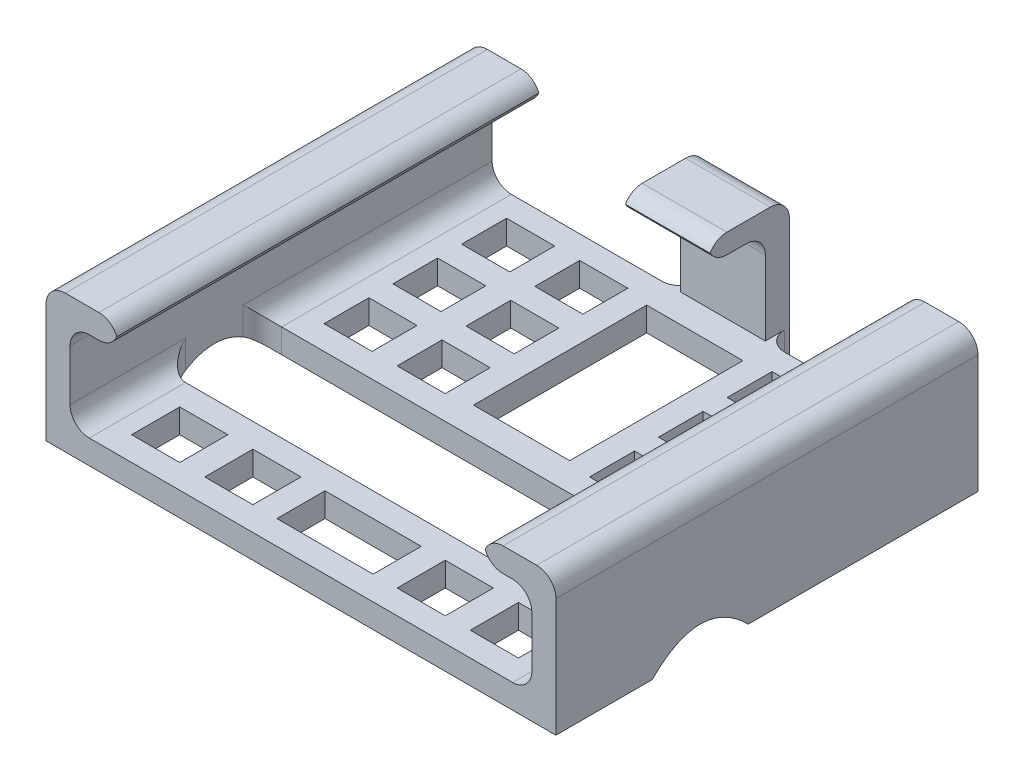
SolidWorks part; units mm, degrees
ref_plane "Front Plane" through (0, 0, 0) normal (0, 0, 1) x (1, 0, 0)
ref_plane "Top Plane" through (0, 0, 0) normal (0, 1, 0) x (1, 0, 0)
ref_plane "Right Plane" through (0, 0, 0) normal (1, 0, 0) x (0, 0, -1)
ref_plane "Plane1" through (15.7583, 0, 0) normal (1, 0, 0) x (0, 0, -1)
sketch "Sketch1" plane through (15.7583, 0, 0) normal (1, 0, 0) x (0, 0, -1)
  line L1 (-13.9868, -18.0983) -> (13.8719, -18.0983)
  line L2 (-13.9868, -18.0983) -> (-13.9868, -16.5108)
  line L3 (-13.9868, -16.5108) -> (13.8719, -16.5108)
  line L4 (13.8719, -18.0983) -> (13.8719, -16.5108)
  line L6 (13.8719, -20.3208) -> (13.8719, -18.7333) construction
  dimension "D1" = 0
extrude "Boss-Extrude1" add sketch "Sketch1" against normal blind 3.175
sketch "Sketch2" plane through (0, -18.0983, 0) normal (0, -1, 0) x (1, 0, 0)
  line L1 (15.7583, -13.8719) -> (17.3458, -13.8719)
  line L2 (15.7583, -13.8719) -> (15.7583, 13.9868)
  line L3 (15.7583, 13.9868) -> (17.3458, 13.9868)
  line L4 (17.3458, -13.8719) -> (17.3458, 13.9868)
extrude "Boss-Extrude2" add sketch "Sketch2" along normal blind 7.493 and the other way blind 1.5875
ref_plane "Plane2" through (0.5183, 0, 0) normal (1, 0, 0) x (0, 0, -1)
mirror "Mirror5" about plane through (0.5183, 0, 0) normal (1, 0, 0) of bodies 102 108
sketch "Sketch6" plane through (15.7583, 0, 0) normal (-1, 0, 0) x (0, 0, 1)
  line L0 (-13.8719, -25.5913) -> (1.2892, -25.5913)
  line L1 (-13.8719, -25.5913) -> (-13.8719, -24.0038)
  line L2 (1.2892, -25.5913) -> (1.2892, -24.0038)
  line L3 (-13.8719, -24.0038) -> (1.2892, -24.0038)
  line L4 (13.9868, -25.5913) -> (7.6359, -25.5913)
  line L5 (13.9868, -25.5913) -> (13.9868, -24.0038)
  line L6 (7.6359, -25.5913) -> (7.6359, -24.0038)
  line L7 (13.9868, -24.0038) -> (7.6359, -24.0038)
  line L8 (-13.8719, -18.0983) -> (-13.8719, -25.5913) construction
  line L9 (13.9868, -25.5913) -> (-13.8719, -25.5913) construction
extrude "Boss-Extrude3" add sketch "Sketch6" along normal blind 30.48
sketch "Sketch12" plane through (15.7583, 0, 0) normal (-1, 0, 0) x (0, 0, 1)
  line L4 (1.2892, -24.0038) -> (7.6359, -24.0038) construction
  line L5 (1.2892, -25.5913) -> (7.6359, -25.5913)
  spline S0 degree 2 poles (1.2892, -25.5913) (4.4626, -22.4163) (7.6359, -25.5913) knots 0 0 0 1 1 1
sketch "Sketch8" plane through (0, -24.0038, 0) normal (0, 1, 0) x (1, 0, 0)
  line L0 (0.5183, 13.8719) -> (0.5183, -1.2892) construction
  line L1 (-12.2452, 0.2983) -> (-9.0702, 0.2983)
  line L2 (-12.2452, 0.2983) -> (-12.2452, 3.2616)
  line L3 (-14.7217, 13.8719) -> (15.7583, 13.8719) construction
  line L4 (-12.2452, 3.2616) -> (-9.0702, 3.2616)
  line L5 (-9.0702, 0.2983) -> (-9.0702, 3.2616)
  line L6 (-14.7217, -1.2892) -> (15.7583, -1.2892) construction
  line L7 (-9.0702, 4.8491) -> (-12.2452, 4.8491)
  line L12 (-14.7217, -1.2892) -> (15.7583, -1.2892) construction
  line L13 (3.6933, 0.5763) -> (-2.6567, 0.5763)
  line L14 (-9.0702, 4.8491) -> (-9.0702, 7.797)
  line L15 (-9.0702, 7.797) -> (-12.2452, 7.797)
  line L16 (3.6933, 0.5763) -> (3.6933, 12.0063)
  line L17 (3.6933, 12.0063) -> (-2.6567, 12.0063)
  line L18 (-2.6567, 0.5763) -> (-2.6567, 12.0063)
  line L19 (3.6933, 0.5763) -> (-2.6567, 12.0063) construction
  line L20 (3.6933, 12.0063) -> (-2.6567, 0.5763) construction
  line L33 (-7.4192, 0.2983) -> (-4.2442, 0.2983)
  line L34 (-7.4192, 0.2983) -> (-7.4192, 3.2616)
  line L35 (-7.4192, 3.2616) -> (-4.2442, 3.2616)
  line L36 (-4.2442, 0.2983) -> (-4.2442, 3.2616)
  line L37 (-12.2452, 4.8491) -> (-12.2452, 7.797)
  line L38 (-12.2452, -9.2234) -> (-9.0702, -9.2234)
  line L39 (-4.2442, 4.8491) -> (-7.4192, 4.8491)
  line L40 (-4.2442, 4.8491) -> (-4.2442, 7.797)
  line L41 (-4.2442, 7.797) -> (-7.4192, 7.797)
  line L42 (-7.4192, 4.8491) -> (-7.4192, 7.797)
  line L43 (-7.4192, 9.3845) -> (-4.2442, 9.3845)
  line L44 (-7.4192, 9.3845) -> (-7.4192, 12.3479)
  line L45 (-7.4192, 12.3479) -> (-4.2442, 12.3479)
  line L46 (-4.2442, 9.3845) -> (-4.2442, 12.3479)
  line L51 (-12.2452, 9.3845) -> (-9.0702, 9.3845)
  line L52 (-12.2452, 9.3845) -> (-12.2452, 12.3479)
  line L53 (-12.2452, 12.3479) -> (-9.0702, 12.3479)
  line L54 (-9.0702, 9.3845) -> (-9.0702, 12.3479)
  line L95 (10.1068, 9.3845) -> (10.1068, 12.3479)
  line L96 (13.2818, 12.3479) -> (10.1068, 12.3479)
  line L97 (13.2818, 9.3845) -> (13.2818, 12.3479)
  line L98 (13.2818, 9.3845) -> (10.1068, 9.3845)
  line L103 (5.2808, 9.3845) -> (5.2808, 12.3479)
  line L104 (8.4558, 12.3479) -> (5.2808, 12.3479)
  line L105 (8.4558, 9.3845) -> (8.4558, 12.3479)
  line L106 (8.4558, 9.3845) -> (5.2808, 9.3845)
  line L107 (8.4558, 4.8491) -> (8.4558, 7.797)
  line L108 (5.2808, 7.797) -> (8.4558, 7.797)
  line L109 (5.2808, 4.8491) -> (5.2808, 7.797)
  line L110 (5.2808, 4.8491) -> (8.4558, 4.8491)
  line L111 (13.2818, 4.8491) -> (13.2818, 7.797)
  line L112 (5.2808, 0.2983) -> (5.2808, 3.2616)
  line L113 (8.4558, 3.2616) -> (5.2808, 3.2616)
  line L114 (8.4558, 0.2983) -> (8.4558, 3.2616)
  line L115 (8.4558, 0.2983) -> (5.2808, 0.2983)
  line L116 (10.1068, 7.797) -> (13.2818, 7.797)
  line L117 (10.1068, 4.8491) -> (10.1068, 7.797)
  line L118 (10.1068, 4.8491) -> (13.2818, 4.8491)
  line L119 (10.1068, 0.2983) -> (10.1068, 3.2616)
  line L120 (13.2818, 3.2616) -> (10.1068, 3.2616)
  line L121 (13.2818, 0.2983) -> (13.2818, 3.2616)
  line L122 (13.2818, 0.2983) -> (10.1068, 0.2983)
  line L123 (-14.7217, -7.6359) -> (15.7583, -7.6359) construction
  line L128 (-16.3092, -13.9868) -> (17.3458, -13.9868) construction
  line L129 (-12.2452, -9.2234) -> (-12.2452, -12.3993)
  line L130 (-12.2452, -12.3993) -> (-9.0702, -12.3993)
  line L131 (-9.0702, -9.2234) -> (-9.0702, -12.3993)
  line L132 (-7.4192, -9.2234) -> (-4.2442, -9.2234)
  line L133 (-7.4192, -9.2234) -> (-7.4192, -12.3993)
  line L134 (-7.4192, -12.3993) -> (-4.2442, -12.3993)
  line L135 (-4.2442, -9.2234) -> (-4.2442, -12.3993)
  line L136 (5.2808, -9.2234) -> (5.2808, -12.3993)
  line L137 (8.4558, -12.3993) -> (5.2808, -12.3993)
  line L138 (8.4558, -9.2234) -> (8.4558, -12.3993)
  line L139 (8.4558, -9.2234) -> (5.2808, -9.2234)
  line L140 (10.1068, -9.2234) -> (10.1068, -12.3993)
  line L141 (13.2818, -12.3993) -> (10.1068, -12.3993)
  line L142 (13.2818, -9.2234) -> (13.2818, -12.3993)
  line L147 (13.2818, -9.2234) -> (10.1068, -9.2234)
  line L148 (-14.7217, 13.8719) -> (15.7583, 13.8719) construction
  line L149 (-2.6567, -9.2234) -> (3.6933, -9.2234)
  line L150 (-2.6567, -9.2234) -> (-2.6567, -12.3993)
  line L151 (-2.6567, -12.3993) -> (3.6933, -12.3993)
  line L152 (3.6933, -9.2234) -> (3.6933, -12.3993)
  line L153 (-2.6567, -9.2234) -> (3.6933, -12.3993) construction
  line L154 (-2.6567, -12.3993) -> (3.6933, -9.2234) construction
  line L155 (-17.0712, 0.2983) -> (-13.8962, 0.2983) [skipped]
  line L156 (-17.0712, 0.2983) -> (-17.0712, 3.2616) [skipped]
  line L157 (-17.0712, 3.2616) -> (-13.8962, 3.2616) [skipped]
  line L158 (-13.8962, 0.2983) -> (-13.8962, 3.2616) [skipped]
  line L159 (-13.8962, 4.8491) -> (-17.0712, 4.8491) [skipped]
  line L160 (-13.8962, 4.8491) -> (-13.8962, 7.797) [skipped]
  line L161 (-13.8962, 7.797) -> (-17.0712, 7.797) [skipped]
  line L162 (-17.0712, 4.8491) -> (-17.0712, 7.797) [skipped]
  line L163 (-17.0712, 9.3845) -> (-13.8962, 9.3845) [skipped]
  line L164 (-17.0712, 9.3845) -> (-17.0712, 12.3479) [skipped]
  line L165 (-17.0712, 12.3479) -> (-13.8962, 12.3479) [skipped]
  line L166 (-13.8962, 9.3845) -> (-13.8962, 12.3479) [skipped]
  point P7 (0.5183, 6.2913)
  point P137 (0.5183, -10.8113)
  dimension "D1" = 1.5875
  dimension "D2" = 1.5875
  dimension "D3" = 1.5875
  dimension "D4" = 1.5875
  dimension "D5" = 1.524
  dimension "D8" = 3
  dimension "D9" = 1.5875
  dimension "D10" = 1.5875
  dimension "D11" = 1.5875
  dimension "D13" = 1.5875
extrude "Cut-Extrude5" cut sketch "Sketch8" against normal blind 1.5875
sketch "Sketch9" plane through (0, 0, -13.8719) normal (0, 0, -1) x (-1, 0, 0)
  line L4 (-0.5183, -24.0038) -> (-0.5183, -25.5913) construction
  line L5 (14.7217, -24.0038) -> (-15.7583, -24.0038) construction
  line L7 (16.3092, -25.5913) -> (-17.3458, -25.5913) construction
  line L9 (-3.3123, -25.5913) -> (2.2757, -25.5913)
  line L10 (-3.3123, -25.5913) -> (-3.3123, -24.0038)
  line L11 (-3.3123, -24.0038) -> (2.2757, -24.0038)
  line L12 (2.2757, -25.5913) -> (2.2757, -24.0038)
  line L13 (-3.3123, -25.5913) -> (2.2757, -24.0038) construction
  line L14 (-3.3123, -24.0038) -> (2.2757, -25.5913) construction
  point P6 (-0.5183, -24.7976)
extrude "Boss-Extrude4" add sketch "Sketch9" along normal blind 1.5875
sketch "Sketch10" plane through (0, -24.0038, 0) normal (0, 1, 0) x (1, 0, 0)
  line L1 (3.3123, 15.4594) -> (-2.2757, 15.4594)
  line L2 (3.3123, 15.4594) -> (3.3123, 13.8719)
  line L3 (3.3123, 13.8719) -> (-2.2757, 13.8719)
  line L4 (-2.2757, 15.4594) -> (-2.2757, 13.8719)
extrude "Boss-Extrude5" add sketch "Sketch10" along normal blind 7.493
sketch "Sketch11" plane through (0, 0, -13.8719) normal (0, 0, 1) x (1, 0, 0)
  line L0 (-2.2757, -16.5108) -> (-2.2757, -24.0038) construction
  line L1 (3.3123, -16.5108) -> (-2.2757, -16.5108)
  line L2 (3.3123, -16.5108) -> (3.3123, -17.8105)
  line L3 (3.3123, -17.8105) -> (-2.2757, -17.8105)
  line L4 (-2.2757, -16.5108) -> (-2.2757, -17.8105)
extrude "Boss-Extrude6" add sketch "Sketch11" along normal blind 3.81
fillet "Fillet1" radius 1.27 22 edges at (-14.7217, -24.7976, 7.6359) (-14.7217, -24.7976, 1.2892) (15.7583, -24.7976, 1.2892) (15.7583, -24.7976, 7.6359) (-14.7217, -18.0983, 0.0574) (15.7583, -18.0983, 0.0574) (15.7583, -24.0038, 10.8113) (-14.7217, -24.0038, 10.8113) (-14.7217, -24.0038, -6.2913) (15.7583, -24.0038, -6.2913) (3.3123, -24.7976, -13.8719) (-2.2757, -24.7976, -13.8719) (0.5183, -17.8105, -13.8719) (17.3458, -16.5108, 0.0574) (-16.3092, -16.5108, 0.0574) (-11.5467, -18.0983, 0.0574) (-11.5467, -16.5108, 0.0574) (12.5833, -18.0983, 0.0574) (12.5833, -16.5108, 0.0574) (0.5183, -17.8105, -10.0619) (0.5183, -16.5108, -10.0619) (0.5183, -16.5108, -15.4594)
extrude "Cut-Extrude6" cut sketch "Sketch12" against normal blind 2.54 and the other way blind 33.02
